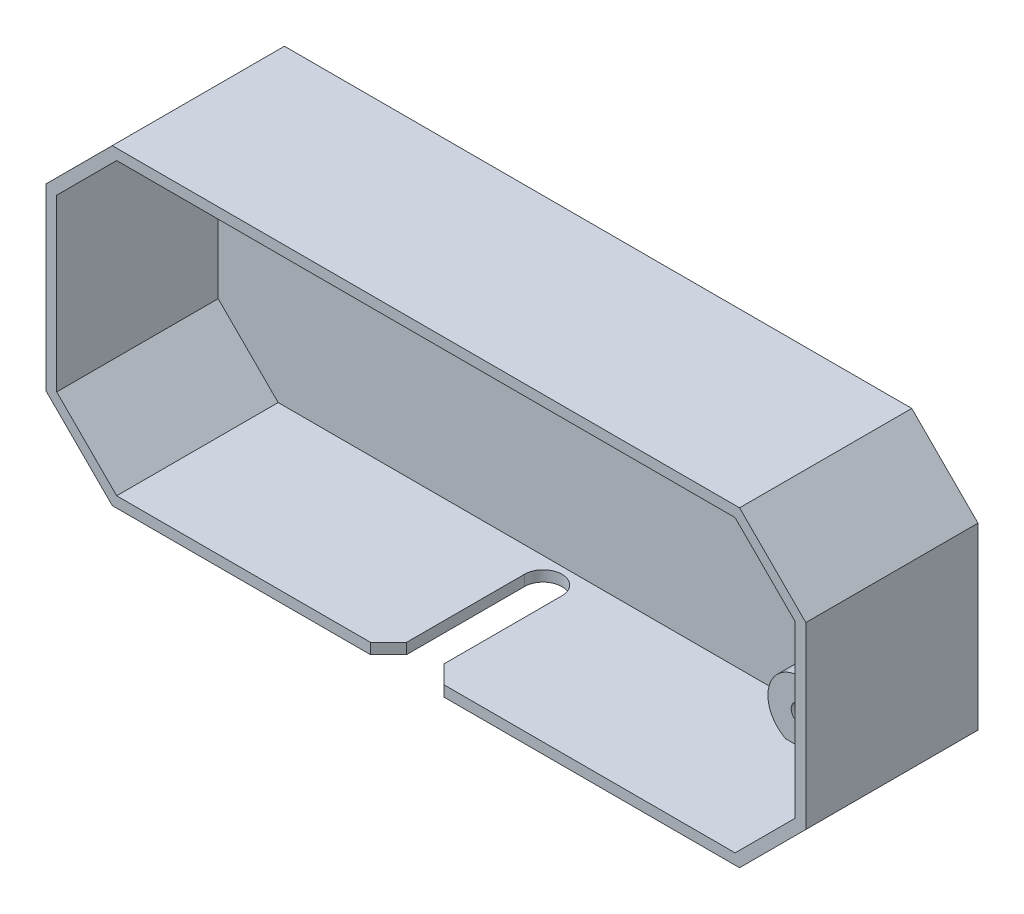
SolidWorks part; units mm, degrees
ref_plane "Front Plane" through (0, 0, 0) normal (0, 0, 1) x (1, 0, 0)
ref_plane "Top Plane" through (0, 0, 0) normal (0, 1, 0) x (1, 0, 0)
ref_plane "Right Plane" through (0, 0, 0) normal (1, 0, 0) x (0, 0, -1)
sketch "Sketch1" plane through (0, 0, 0) normal (0, 0, 1) x (1, 0, 0)
  line L1 (-28.3844, -11.6458) -> (28.3844, -11.6458)
  line L2 (-28.3844, -11.6458) -> (-28.3844, 11.6458)
  line L3 (-28.3844, 11.6458) -> (28.3844, 11.6458)
  line L4 (28.3844, -11.6458) -> (28.3844, 11.6458)
  line L5 (-28.3844, -11.6458) -> (28.3844, 11.6458) construction
  line L6 (-28.3844, 11.6458) -> (28.3844, -11.6458) construction
  point P0 (0, 0)
  dimension "D1" = 56.7688
  dimension "D2" = 23.2916
extrude "Boss-Extrude1" add sketch "Sketch1" along normal blind 0.8
sketch "Sketch2" plane through (0, 0, 0.8) normal (0, 0, 1) x (1, 0, 0)
  line L0 (-28.3844, -6.6961) -> (-23.4347, -11.6458)
  line L1 (-28.3844, 11.6458) -> (-28.3844, -11.6458) construction
  line L2 (-28.3844, 6.6961) -> (-23.4347, 11.6458)
  line L3 (28.3844, 11.6458) -> (-28.3844, 11.6458) construction
  line L4 (-23.4347, 11.6458) -> (-28.3844, 11.6458)
  line L5 (-28.3844, 11.6458) -> (-28.3844, 6.6961)
  line L6 (-28.3844, -11.6458) -> (28.3844, -11.6458) construction
  line L7 (-23.4347, -11.6458) -> (-28.3844, -11.6458)
  line L8 (-28.3844, -11.6458) -> (-28.3844, -6.6961)
  line L9 (23.4347, -11.6458) -> (28.3844, -6.6961)
  line L10 (28.3844, -11.6458) -> (28.3844, 11.6458) construction
  line L11 (28.3844, -6.6961) -> (28.3844, -11.6458)
  line L12 (28.3844, -11.6458) -> (23.4347, -11.6458)
  line L13 (23.4347, 11.6458) -> (28.3844, 6.6961)
  line L14 (28.3844, 6.6961) -> (28.3844, 11.6458)
  line L15 (28.3844, 11.6458) -> (23.4347, 11.6458)
  dimension "D1" = 7
  dimension "D2" = 7
  dimension "D3" = 7
  dimension "D4" = 7
  dimension "D5" = 45
  dimension "D6" = 45
  dimension "D7" = 45
  dimension "D8" = 45
extrude "Cut-Extrude1" cut sketch "Sketch2" against normal through all
sketch "Sketch3" plane through (0, 0, 0.8) normal (0, 0, 1) x (1, 0, 0)
  line L0 (23.4347, 11.6458) -> (-23.4347, 11.6458)
  line L1 (-23.4347, 11.6458) -> (-28.3844, 6.6961)
  line L2 (-28.3844, 6.6961) -> (-28.3844, -6.6961)
  line L3 (-28.3844, -6.6961) -> (-23.4347, -11.6458)
  line L4 (-23.4347, -11.6458) -> (23.4347, -11.6458)
  line L5 (23.4347, -11.6458) -> (28.3844, -6.6961)
  line L6 (28.3844, -6.6961) -> (28.3844, 6.6961)
  line L7 (28.3844, 6.6961) -> (23.4347, 11.6458)
  line L48 (-23.1033, 10.8458) -> (-27.5844, 6.3647)
  line L49 (-27.5844, 6.3647) -> (-27.5844, -6.3647)
  line L50 (-27.5844, -6.3647) -> (-23.1033, -10.8458)
  line L51 (-23.1033, -10.8458) -> (23.1033, -10.8458)
  line L52 (23.1033, -10.8458) -> (27.5844, -6.3647)
  line L53 (27.5844, -6.3647) -> (27.5844, 6.3647)
  line L54 (27.5844, 6.3647) -> (23.1033, 10.8458)
  line L55 (23.1033, 10.8458) -> (-23.1033, 10.8458)
  line L56 (-23.1033, 10.8458) -> (-27.5844, 6.3647)
  line L57 (-27.5844, 6.3647) -> (-27.5844, -6.3647)
  line L58 (-27.5844, -6.3647) -> (-23.1033, -10.8458)
  line L59 (-23.1033, -10.8458) -> (23.1033, -10.8458)
  line L60 (23.1033, -10.8458) -> (27.5844, -6.3647)
  line L61 (27.5844, -6.3647) -> (27.5844, 6.3647)
  line L62 (27.5844, 6.3647) -> (23.1033, 10.8458)
  line L63 (23.1033, 10.8458) -> (-23.1033, 10.8458)
  dimension "D1" = 0.8
  dimension "D2" = 0.8
extrude "Boss-Extrude2" add sketch "Sketch3" along normal blind 12.065
sketch "Sketch4" plane through (0, 0, 0.8) normal (0, 0, 1) x (1, 0, 0)
  line L0 (23.1033, 10.8458) -> (-23.1033, 10.8458) construction
  line L1 (-23.1033, -10.8458) -> (23.1033, -10.8458) construction
  line L2 (-27.5844, 6.3647) -> (-27.5844, -6.3647) construction
  line L3 (27.5844, -6.3647) -> (27.5844, 6.3647) construction
  circle A0 centre (-21.7424, 8.8138) radius 2.413
  circle A1 centre (18.6944, -8.6868) radius 2.413
  dimension "D1" = 4.826
  dimension "D2" = 4.826
  dimension "D3" = 2.032
  dimension "D4" = 2.159
  dimension "D5" = 8.89
  dimension "D6" = 5.842
extrude "Boss-Extrude3" add sketch "Sketch4" along normal blind 2.794
sketch "Sketch5" plane through (0, 0, 3.594) normal (0, 0, 1) x (1, 0, 0)
  circle A0 centre (-21.7424, 8.8138) radius 0.6731
  circle A1 centre (18.6944, -8.6868) radius 0.6731
  dimension "D1" = 1.3462
  dimension "D2" = 1.3462
extrude "Cut-Extrude2" cut sketch "Sketch5" against normal up to surface (2.794 mm away) up to face at (1.5551, -0.9951, 0.8)
sketch "Sketch6" plane through (0, -11.6458, 0) normal (0, -1, 0) x (-1, 0, 0)
  line L0 (-1.347, -12.865) -> (4.141, -12.865)
  line L1 (23.4347, -12.865) -> (-23.4347, -12.865) construction
  line L3 (0, -11.518) -> (0, -2.705)
  line L4 (2.794, -11.518) -> (4.141, -12.865)
  line L6 (0, -11.518) -> (-1.347, -12.865)
  line L8 (2.794, -2.705) -> (2.794, -11.518)
  arc A0 (2.794, -2.705) -> (0, -2.705) centre (1.397, -2.705) ccw
  dimension "D2" = 1.397
  dimension "D1" = 45
  dimension "D3" = 2.794
  dimension "D4" = 1.905
  dimension "D5" = 1.905
  dimension "D6" = 45
  dimension "D7" = 10.16
extrude "Cut-Extrude3" cut sketch "Sketch6" against normal blind 2.794
